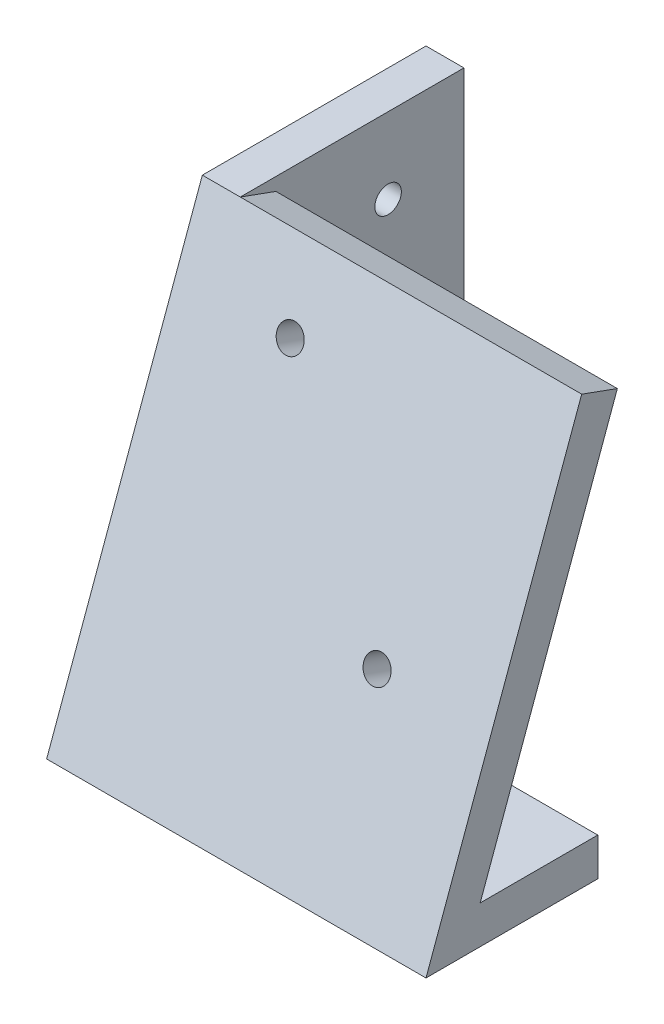
SolidWorks part; units mm, degrees
material "ABS"
ref_plane "Front Plane" through (0, 0, 0) normal (0, 0, 1) x (1, 0, 0)
ref_plane "Top Plane" through (0, 0, 0) normal (0, 1, 0) x (1, 0, 0)
ref_plane "Right Plane" through (0, 0, 0) normal (1, 0, 0) x (0, 0, -1)
sketch "Sketch1" plane through (0, 0, 0) normal (1, 0, 0) x (0, 0, -1)
  line L0 (0, 0) -> (-50, 0)
  line L1 (-50, 0) -> (-29.4788, 56.3816)
  line L2 (-29.4788, 56.3816) -> (-24.7803, 54.6715)
  line L3 (-24.7803, 54.6715) -> (-42.8593, 5)
  line L4 (-42.8593, 5) -> (0, 5)
  line L5 (0, 5) -> (0, 0)
  dimension "D1" = 60
  dimension "D2" = 50
  dimension "D3" = 70
  dimension "D4" = 5
  dimension "D5" = 5
extrude "Main" add sketch "Sketch1" along normal mid plane 50
sketch "Sketch2" plane through (0, 0, 0) normal (0, 0, -1) x (-1, 0, 0)
  line L0 (-25, 56.3816) -> (25, 56.3816) construction
  line L1 (-25, 0) -> (-20, 0)
  line L2 (-25, 0) -> (-25, 56.3816)
  line L3 (-25, 56.3816) -> (-20, 56.3816)
  line L4 (-20, 0) -> (-20, 56.3816)
  dimension "D1" = 5
extrude "Back" add sketch "Sketch2" against normal up to next
hole_wizard "Base Holes" positions "3DSketch4" profile "Sketch5" hole size "Ø3.5" standard "ANSI Metric"
sketch3d "3DSketch4"
  line L0 (-25, 5, 0) -> (-25, 5, 42.8593) construction
  line L4 (20, 5, 42.8593) -> (-25, 5, 42.8593) construction
  point P0 (10, 5, 32.6993)
  point P2 (-10, 5, 32.6993)
  dimension "D1" = 15
  dimension "D2" = 15
  dimension "D3" = 10.16
  dimension "D4" = 10.16
sketch "Sketch5" plane through (10, 5, 32.6993) normal (1, 0, 0) x (0, 0, 1)
  line L0 (0, 0) -> (0, 5)
  line L1 (0, 5) -> (1.75, 5)
  line L2 (1.75, 5) -> (1.75, 0)
  line L5 (1.75, 0) -> (0, 0)
  line L10 (0, 5) -> (-1.75, 5) construction
  line L11 (0, -6.35) -> (0, 107.95) construction
  dimension "Hole Dia." = 3.5
  dimension "Hole Depth" = 5
  dimension "Drill Angle" = 180
hole_wizard "BackPanelHoles" positions "Sketch6" profile "Sketch7" hole size "Ø1.0" standard "ANSI Metric"
sketch "Sketch6" plane through (20, 0, 0) normal (-1, 0, 0) x (0, 0, 1)
  line L0 (29.4788, 56.3816) -> (0, 56.3816) construction
  line L1 (0, 5) -> (0, 56.3816) construction
  line L2 (50, 0) -> (0, 0) construction
  point P0 (10, 46.3816)
  point P2 (25, 20)
  dimension "D1" = 10
  dimension "D2" = 10
  dimension "D3" = 20
  dimension "D4" = 25
sketch "Sketch7" plane through (20, 46.3816, 10) normal (0, 1, 0) x (0, 0, 1)
  line L0 (0, 0) -> (0, 5)
  line L1 (0, 5) -> (1.75, 5)
  line L2 (1.75, 5) -> (1.75, 0)
  line L5 (1.75, 0) -> (0, 0)
  line L10 (0, 5) -> (-1.75, 5) construction
  line L11 (0, -6.35) -> (0, 107.95) construction
  dimension "Hole Dia." = 3.5
  dimension "Hole Depth" = 5
  dimension "Drill Angle" = 180
hole_wizard "Ø1.0mm Dowel Hole1" positions "3DSketch5" profile "Sketch8" hole size "Ø1.0" standard "ANSI Metric"
sketch3d "3DSketch5"
  line L1 (20, 56.3816, 29.4788) -> (-25, 56.3816, 29.4788) construction
  line L2 (25, 0, 50) -> (-25, 0, 50) construction
  line L3 (-25, 56.3816, 29.4788) -> (-25, 0, 50) construction
  line L4 (25, 56.3816, 29.4788) -> (25, 0, 50) construction
  point P0 (-10, 46.9846, 32.899)
  point P2 (10, 23.4923, 41.4495)
  dimension "D1" = 15
  dimension "D2" = 10
  dimension "D3" = 25
  dimension "D4" = 15
sketch "Sketch8" plane through (-10, 46.9846, 32.899) normal (1, 0, 0) x (0, -0.9397, 0.342)
  line L0 (0, 0) -> (0, 5)
  line L1 (0, 5) -> (1.75, 5)
  line L2 (1.75, 5) -> (1.75, 0)
  line L5 (1.75, 0) -> (0, 0)
  line L10 (0, 5) -> (-1.75, 5) construction
  line L11 (0, -6.35) -> (0, 107.95) construction
  dimension "Hole Dia." = 3.5
  dimension "Hole Depth" = 5
  dimension "Drill Angle" = 180
ref_plane "Midplane" through (0, 0, 0) normal (-1, 0, 0) x (0, 0, 1)
mirror "Mirror1" about plane through (0, 0, 0) normal (-1, 0, 0) of "BackPanelHoles", "Back"
sketch "Sketch9" plane through (20, 0, 0) normal (-1, 0, 0) x (0, 0, 1)
  line L0 (29.4788, 56.3816) -> (0, 56.3816)
  line L1 (0, 56.3816) -> (0, 5)
  line L2 (0, 5) -> (42.8593, 5)
  line L3 (42.8593, 5) -> (24.7803, 54.6715)
  line L4 (24.7803, 54.6715) -> (29.4788, 56.3816)
extrude "Mirror Cut" cut sketch "Sketch9" against normal up to next
sketch "Sketch10" plane through (0, 5, 0) normal (0, 1, 0) x (1, 0, 0)
  line L0 (25, -42.8593) -> (25, 0) construction
  line L1 (-20, 0) -> (25, 0)
  line L2 (-20, 0) -> (-20, -5)
  line L3 (-20, -5) -> (25, -5)
  line L4 (25, 0) -> (25, -5)
  dimension "D1" = 5
extrude "BatteryCut" cut sketch "Sketch10" against normal up to next
sketch "Sketch11" plane through (0, 5, 0) normal (0, 1, 0) x (1, 0, 0)
  line L0 (-20, -5) -> (25, -5) construction
  line L1 (-8.3622, -5) -> (25, -5)
  line L2 (-8.3622, -5) -> (-8.3622, -27.3622)
  line L3 (-8.3622, -27.3622) -> (25, -27.3622)
  line L4 (25, -5) -> (25, -27.3622)
  line L5 (-4.3622, -27.3622) -> (-7.3622, -27.3622) construction
  line L6 (-7.3622, -27.3622) -> (-7.3622, -11.3622) construction
  line L8 (25, -42.8593) -> (25, -5) construction
  dimension "D1" = 1
extrude "Cut-Extrude1" cut sketch "Sketch11" against normal through all
